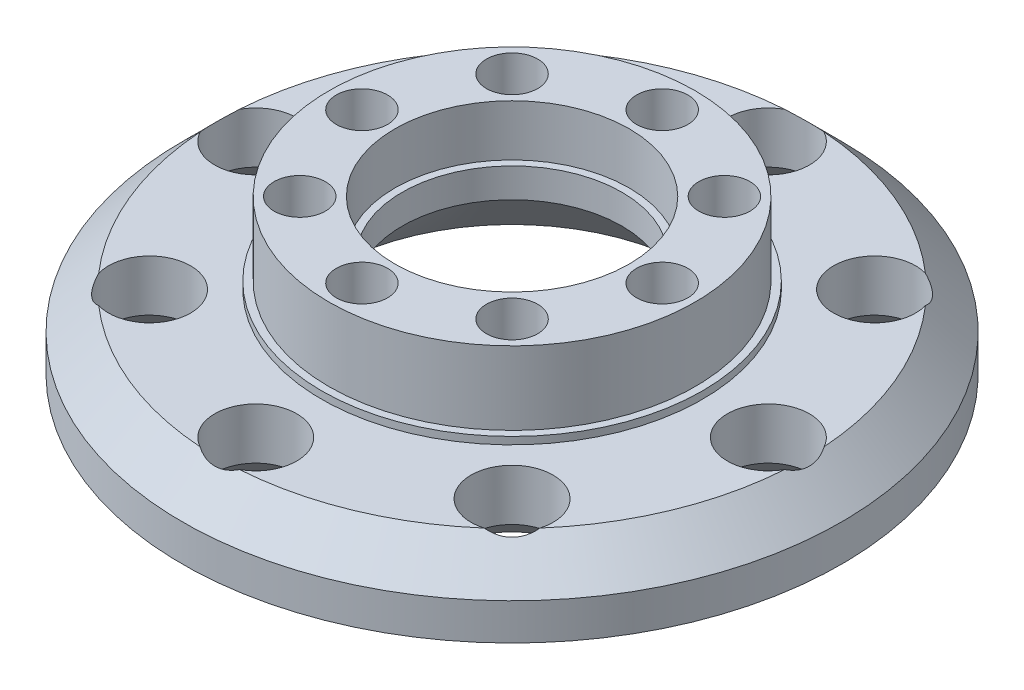
SolidWorks part; units mm, degrees
ref_plane "Front Plane" through (0, 0, 0) normal (0, 0, 1) x (1, 0, 0)
ref_plane "Top Plane" through (0, 0, 0) normal (0, 1, 0) x (1, 0, 0)
ref_plane "Right Plane" through (0, 0, 0) normal (1, 0, 0) x (0, 0, -1)
sketch "Sketch1" plane through (0, 0, 0) normal (0, 1, 0) x (1, 0, 0)
  circle A0 centre (0, 0) radius 25
  circle A1 centre (0, 0) radius 17.5
  point P24 (0.5, 0)
extrude "Boss-Extrude1" add sketch "Sketch1" along normal blind 10
sketch "Sketch2" plane through (0, 0, 0) normal (0, -1, 0) x (1, 0, 0)
  circle A0 centre (0, 0) radius 35
  circle A1 centre (-35, 0) radius 5.6
  circle A2 centre (-24.7487, 24.7487) radius 5.6
  circle A3 centre (0, 35) radius 5.6
  circle A4 centre (24.7487, 24.7487) radius 5.6
  circle A5 centre (35, 0) radius 5.6
  circle A6 centre (24.7487, -24.7487) radius 5.6
  circle A7 centre (0, -35) radius 5.6
  circle A8 centre (-24.7487, -24.7487) radius 5.6
  circle A9 centre (0, 0) radius 45
  point P21 (0, 0)
  dimension "D1" = 8
extrude "Boss-Extrude2" add sketch "Sketch2" along normal blind 10
chamfer "Chamfer1" distance 5 angle 45 1 edges at (0, 0, -45)
sketch "Sketch4" plane through (0, 10, 0) normal (0, 1, 0) x (1, 0, 0)
  circle A0 centre (0, 0) radius 16
  circle A2 centre (0, 0) radius 17.5
extrude "Boss-Extrude4" add sketch "Sketch4" against normal blind 20
sketch "Sketch5" plane through (0, 10, 0) normal (0, 1, 0) x (1, 0, 0)
  circle A0 centre (0, 0) radius 15
  circle A1 centre (0, 0) radius 16
extrude "Boss-Extrude5" add sketch "Sketch5" against normal blind 13 from offset 7 offset against normal yes
chamfer "Chamfer3" distance 10 angle 45 1 edges at (0, -10, 15)
sketch "Sketch7" plane through (0, 10, 0) normal (0, 1, 0) x (1, 0, 0)
  circle A0 centre (0, 0) radius 25
  circle A1 centre (0, 0) radius 16
extrude "Boss-Extrude6" add sketch "Sketch7" along normal blind 1
sketch "Sketch8" plane through (0, 3, 0) normal (0, 1, 0) x (1, 0, 0)
  circle A0 centre (0, 0) radius 16
  circle A1 centre (0, 0) radius 15
extrude "Boss-Extrude7" add sketch "Sketch8" along normal blind 1
sketch "Sketch9" plane through (0, 0, 0) normal (0, 1, 0) x (1, 0, 0)
  circle A0 centre (0, 0) radius 26
extrude "Boss-Extrude8" add sketch "Sketch9" along normal blind 1
sketch "Sketch10" plane through (0, 1, 0) normal (0, 1, 0) x (1, 0, 0)
  circle A0 centre (0, 0) radius 15
extrude "Cut-Extrude1" cut sketch "Sketch10" against normal blind 18
chamfer "Chamfer4" distance 3 angle 45 8 edges at (-24.7487, -10, -30.3487) (0, -10, -40.6) (24.7487, -10, -30.3487) (35, -10, -5.6) (24.7487, -10, 19.1487) (0, -10, 29.4) (-24.7487, -10, 19.1487) (-35, -10, -5.6)
sketch "Sketch11" plane through (0, 11, 0) normal (0, 1, 0) x (1, 0, 0)
  circle A3 centre (-20.5, 0) radius 3.5
  circle A4 centre (-14.4957, 14.4957) radius 3.5
  circle A5 centre (0, 20.5) radius 3.5
  circle A6 centre (14.4957, 14.4957) radius 3.5
  circle A7 centre (20.5, 0) radius 3.5
  circle A8 centre (14.4957, -14.4957) radius 3.5
  circle A9 centre (0, -20.5) radius 3.5
  circle A10 centre (-14.4957, -14.4957) radius 3.5
  point P27 (0, 0)
  dimension "D1" = 8
extrude "Cut-Extrude2" cut sketch "Sketch11" against normal blind 5
